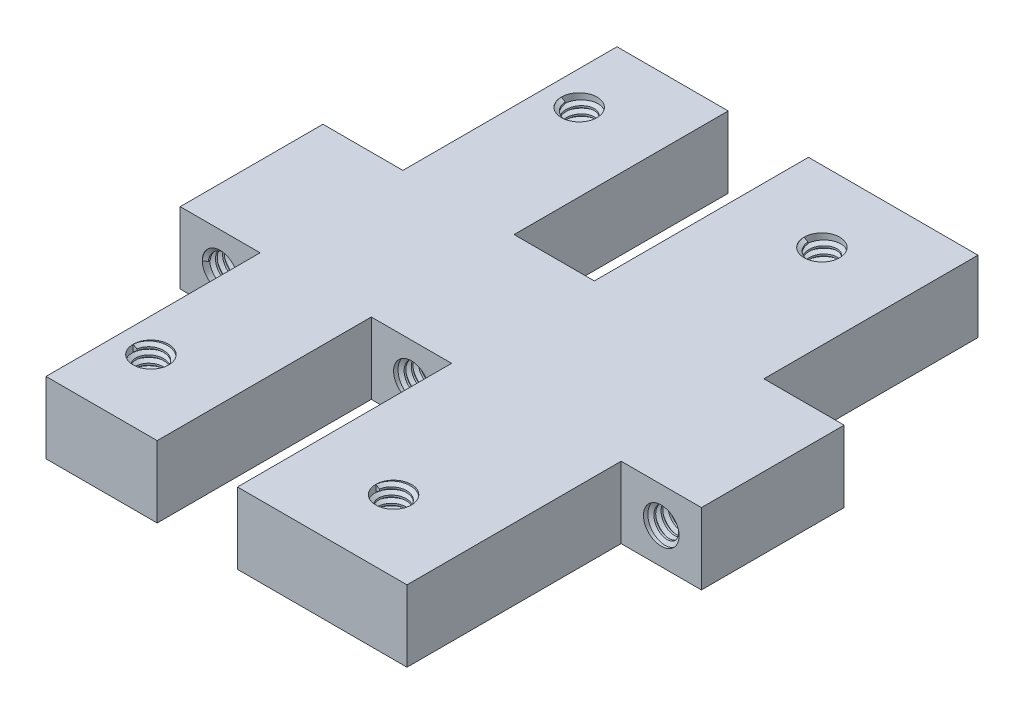
SolidWorks part; units mm, degrees
material "Plain Carbon Steel"
ref_plane "Front Plane" through (0, 0, 0) normal (0, 0, 1) x (1, 0, 0)
ref_plane "Top Plane" through (0, 0, 0) normal (0, 1, 0) x (1, 0, 0)
ref_plane "Right Plane" through (0, 0, 0) normal (1, 0, 0) x (0, 0, -1)
sketch "Sketch1" plane through (0, 0, 0) normal (0, 1, 0) x (1, 0, 0)
  line L0 (0, 51.3938) -> (0, -59.5745) construction
  line L1 (-34.925, 25.4) -> (34.925, 25.4)
  line L2 (-34.925, 25.4) -> (-34.925, -25.4)
  line L3 (-34.925, -25.4) -> (34.925, -25.4)
  line L4 (34.925, 25.4) -> (34.925, -25.4)
  line L5 (-83.1273, 0) -> (79.8286, 0) construction
  dimension "D1" = 50.8
  dimension "D2" = 69.85
extrude "Boss-Extrude1" add sketch "Sketch1" along normal blind 12.7
ref_plane "Plane1" through (22.225, 0, 0) normal (1, 0, 0) x (0, 0, -1)
ref_plane "Plane2" through (-22.225, 0, 0) normal (1, 0, 0) x (0, 0, -1)
sketch "Sketch3" plane through (0, 12.7, 0) normal (0, 1, 0) x (1, 0, 0)
  line L0 (-34.925, -25.4) -> (34.925, -25.4) construction
  line L1 (15.0813, -25.4) -> (29.3688, -25.4)
  line L2 (15.0813, -25.4) -> (15.0813, -12.7)
  line L3 (15.0813, -12.7) -> (29.3688, -12.7)
  line L4 (29.3688, -25.4) -> (29.3688, -12.7)
  line L5 (34.925, 25.4) -> (-34.925, 25.4) construction
  line L6 (-29.3687, -25.4) -> (-15.0812, -25.4)
  line L7 (-29.3687, -25.4) -> (-29.3687, -12.7)
  line L8 (-29.3687, -12.7) -> (-15.0813, -12.7)
  line L9 (-15.0812, -25.4) -> (-15.0813, -12.7)
  line L10 (-29.3687, 25.4) -> (-15.0813, 25.4)
  line L11 (-29.3687, 25.4) -> (-29.3687, 12.7)
  line L12 (-29.3687, 12.7) -> (-15.0812, 12.7)
  line L13 (-15.0813, 25.4) -> (-15.0812, 12.7)
  line L14 (-22.225, 31.6602) -> (-22.225, -34.0161) construction
  line L15 (15.0813, 25.4) -> (29.3687, 25.4)
  line L16 (15.0813, 25.4) -> (15.0812, 12.7)
  line L17 (15.0812, 12.7) -> (29.3687, 12.7)
  line L18 (29.3687, 25.4) -> (29.3687, 12.7)
  line L19 (-22.225, -6.985) -> (-22.225, 6.985) construction
  line L20 (22.225, 30.314) -> (22.225, -34.0161) construction
  line L21 (22.225, -6.985) -> (22.225, 6.985) construction
  dimension "D1" = 12.7
  dimension "D2" = 14.2875
  dimension "D3" = 14.2875
  dimension "D4" = 12.7
  dimension "D5" = 12.7
  dimension "D6" = 14.2875
  dimension "D7" = 14.2875
  dimension "D8" = 12.7
extrude "Cut-Extrude1" cut sketch "Sketch3" against normal blind 12.7
sketch "Sketch4" plane through (0, 0, -12.7) normal (0, 0, -1) x (-1, 0, 0)
  line L0 (-22.225, 6.985) -> (-22.225, -6.985) construction
  line L1 (-34.925, 6.35) -> (43.2714, 6.35) construction
  line L2 (-34.925, 12.7) -> (-34.925, 0) construction
  line L3 (0, 6.985) -> (0, -6.985) construction
  circle A0 centre (-22.225, 6.35) radius 3.175
  circle A1 centre (22.225, 6.35) radius 3.175
  dimension "D1" = 6.35
extrude "Cut-Extrude2" cut sketch "Sketch4" against normal through all
sketch "Sketch6" plane through (0, 12.7, 0) normal (0, 1, 0) x (1, 0, 0)
  line L0 (-34.925, -25.4) -> (-29.3687, -25.4) construction
  line L1 (-34.925, 25.4) -> (-49.149, 25.4)
  line L2 (-34.925, 25.4) -> (-34.925, -25.4)
  line L3 (-34.925, -25.4) -> (-49.149, -25.4)
  line L4 (-49.149, 25.4) -> (-49.149, -25.4)
  dimension "D1" = 14.224
extrude "Boss-Extrude2" add sketch "Sketch6" against normal blind 12.7
sketch "Sketch9" plane through (0, 12.7, 0) normal (0, 1, 0) x (1, 0, 0)
  line L0 (-29.3687, 25.4) -> (-29.3687, 12.7) construction
  line L1 (-49.149, 25.4) -> (-29.3688, 25.4)
  line L2 (-49.149, 25.4) -> (-49.149, 50.8)
  line L3 (-49.149, 50.8) -> (-29.3687, 50.8)
  line L4 (-29.3688, 25.4) -> (-29.3687, 50.8)
  line L5 (-15.0813, 25.4) -> (15.0813, 25.4)
  line L6 (-15.0813, 25.4) -> (-15.0813, 50.8)
  line L7 (-15.0813, 50.8) -> (15.0813, 50.8)
  line L8 (15.0813, 25.4) -> (15.0813, 50.8)
  line L9 (15.0813, 25.4) -> (15.0812, 12.7) construction
  line L10 (-49.149, 25.4) -> (-49.149, -25.4) construction
  line L11 (-29.3687, -25.4) -> (-49.149, -25.4)
  line L12 (-29.3687, -25.4) -> (-29.3687, -50.8)
  line L13 (-29.3687, -50.8) -> (-49.149, -50.8)
  line L14 (-49.149, -25.4) -> (-49.149, -50.8)
  line L15 (15.0813, -25.4) -> (-15.0813, -25.4)
  line L16 (15.0813, -25.4) -> (15.0813, -50.8)
  line L17 (15.0813, -50.8) -> (-15.0812, -50.8)
  line L18 (-15.0813, -25.4) -> (-15.0812, -50.8)
  line L19 (-15.0812, -25.4) -> (-15.0813, -12.7) construction
  dimension "D1" = 25.4
  dimension "D2" = 25.4
  dimension "D3" = 25.4
  dimension "D4" = 25.4
extrude "Boss-Extrude3" add sketch "Sketch9" against normal blind 12.7
sketch "Sketch7" plane through (0, 12.7, 0) normal (0, 1, 0) x (1, 0, 0)
  line L0 (-29.3687, -38.1) -> (40.9011, -38.1) construction
  line L2 (-42.799, -25.4) -> (-42.799, 7.4831) construction
  line L3 (-15.0812, -50.8) -> (15.0813, -50.8) construction
  line L5 (-6.985, 0) -> (6.985, 0) construction
  line L6 (-49.149, 50.8) -> (-49.149, -50.8) construction
  line L7 (34.925, -25.4) -> (34.925, 25.4) construction
  circle A0 centre (-43.18, -38.1) radius 3.175
  circle A1 centre (0, -38.1) radius 3.175
  circle A2 centre (-43.18, 38.1) radius 3.175
  circle A3 centre (0, 38.1) radius 3.175
  dimension "D1" = 6.35
  dimension "D2" = 6.35
  dimension "D3" = 6.35
  dimension "D4" = 34.925
  dimension "D5" = 78.105
  dimension "D6" = 12.7
extrude "Cut-Extrude3" cut sketch "Sketch7" against normal blind 12.7
thread "Thread1" pitch 1.27 method extrude profile "Thread Profile1" start angle 0, offset 0, length 0, pitch 1.27, diameter 6.35
ref_plane "Plane3" through (-46.355, 12.7, 38.1) normal (0, 0, 1) x (-1, 0, 0)
sketch "Thread Profile1" plane through (-46.355, 12.7, 38.1) normal (0, 0, 1) x (-1, 0, 0)
  line L0 (0, 0) -> (0, 1.27) construction
  line L11 (0, 0) -> (0, 1.1112)
  line L12 (0, 1.1112) -> (-0.6874, 0.7144)
  line L13 (-0.6874, 0.7144) -> (-0.6874, 0.3969)
  line L15 (-0.6874, 0.3969) -> (0, 0)
  line L17 (-0.6874, 0.5556) -> (0, 0.5556) construction
  point P2 (0, 0)
  dimension "Pitch" = 1.27
  dimension "Profile_Angle" = 60
  dimension "Profile_Land" = 0.3175
  dimension "Profile_Height" = 0.6874
thread "Thread2" pitch 1.27 method extrude profile "Thread Profile2" start angle 0, offset 0, length 0, pitch 1.27, diameter 6.35
ref_plane "Plane4" through (-3.175, 12.7, 38.1) normal (0, 0, 1) x (-1, 0, 0)
sketch "Thread Profile2" plane through (-3.175, 12.7, 38.1) normal (0, 0, 1) x (-1, 0, 0)
  line L0 (0, 0) -> (0, 1.27) construction
  line L11 (0, 0) -> (0, 1.1112)
  line L12 (0, 1.1112) -> (-0.6874, 0.7144)
  line L13 (-0.6874, 0.7144) -> (-0.6874, 0.3969)
  line L15 (-0.6874, 0.3969) -> (0, 0)
  line L17 (-0.6874, 0.5556) -> (0, 0.5556) construction
  point P2 (0, 0)
  dimension "Pitch" = 1.27
  dimension "Profile_Angle" = 60
  dimension "Profile_Land" = 0.3175
  dimension "Profile_Height" = 0.6874
mirror "Mirror1" about plane through (0, 0, 0) normal (0, 0, 1) of "Thread2", "Thread1"
thread "Thread3" pitch 1.27 method extrude profile "Thread Profile3" start angle 0, offset 0, length 0, pitch 1.27, diameter 6.35
ref_plane "Plane5" through (-19.05, 6.35, -12.7) normal (0, -1, 0) x (1, 0, 0)
sketch "Thread Profile3" plane through (-19.05, 6.35, -12.7) normal (0, -1, 0) x (1, 0, 0)
  line L0 (0, 0) -> (0, 1.27) construction
  line L11 (0, 0) -> (0, 1.1112)
  line L12 (0, 1.1112) -> (-0.6874, 0.7144)
  line L13 (-0.6874, 0.7144) -> (-0.6874, 0.3969)
  line L15 (-0.6874, 0.3969) -> (0, 0)
  line L17 (-0.6874, 0.5556) -> (0, 0.5556) construction
  point P2 (0, 0)
  dimension "Pitch" = 1.27
  dimension "Profile_Angle" = 60
  dimension "Profile_Land" = 0.3175
  dimension "Profile_Height" = 0.6874
thread "Thread4" pitch 1.27 method extrude profile "Thread Profile4" start angle 0, offset 0, length 0, pitch 1.27, diameter 6.35
ref_plane "Plane6" through (25.4, 6.35, -12.7) normal (0, -1, 0) x (1, 0, 0)
sketch "Thread Profile4" plane through (25.4, 6.35, -12.7) normal (0, -1, 0) x (1, 0, 0)
  line L0 (0, 0) -> (0, 1.27) construction
  line L11 (0, 0) -> (0, 1.1112)
  line L12 (0, 1.1112) -> (-0.6874, 0.7144)
  line L13 (-0.6874, 0.7144) -> (-0.6874, 0.3969)
  line L15 (-0.6874, 0.3969) -> (0, 0)
  line L17 (-0.6874, 0.5556) -> (0, 0.5556) construction
  point P2 (0, 0)
  dimension "Pitch" = 1.27
  dimension "Profile_Angle" = 60
  dimension "Profile_Land" = 0.3175
  dimension "Profile_Height" = 0.6874
sketch "Sketch10" plane through (0, 12.7, 0) normal (0, 1, 0) x (1, 0, 0)
  line L1 (29.3687, 25.4) -> (34.925, 25.4)
  line L2 (29.3687, 25.4) -> (29.3687, -25.4)
  line L3 (29.3687, -25.4) -> (34.925, -25.4)
  line L4 (34.925, 25.4) -> (34.925, -25.4)
extrude "Cut-Extrude4" cut sketch "Sketch10" against normal blind 12.7
sketch "Sketch11" plane through (0, 12.7, 0) normal (0, 1, 0) x (1, 0, 0)
  line L0 (-49.149, 50.8) -> (-49.149, -50.8) construction
  line L1 (-49.149, 12.7) -> (-63.373, 12.7)
  line L2 (-49.149, 12.7) -> (-49.149, -12.7)
  line L3 (-49.149, -12.7) -> (-63.373, -12.7)
  line L4 (-63.373, 12.7) -> (-63.373, -12.7)
  line L5 (-29.3687, 12.7) -> (-15.0812, 12.7) construction
  line L6 (-15.0813, -12.7) -> (-29.3687, -12.7) construction
  dimension "D1" = 14.224
extrude "Boss-Extrude4" add sketch "Sketch11" against normal blind 12.7
sketch "Sketch12" plane through (0, 0, 12.7) normal (0, 0, 1) x (1, 0, 0)
  line L0 (-56.261, 12.7) -> (-56.261, 0) construction
  line L1 (-63.373, 12.7) -> (-49.149, 12.7) construction
  line L2 (-63.373, 0) -> (-49.149, 0) construction
  line L3 (-63.373, 6.35) -> (-49.149, 6.35) construction
  line L4 (-63.373, 0) -> (-63.373, 12.7) construction
  line L5 (-49.149, 0) -> (-49.149, 12.7) construction
  circle A0 centre (-56.261, 6.35) radius 3.175
  dimension "D1" = 6.35
extrude "Cut-Extrude5" cut sketch "Sketch12" against normal through all
thread "Thread6" pitch 1.27 method extrude profile "Thread Profile6" start angle 0, offset 0, length 0, pitch 1.27, diameter 6.35
ref_plane "Plane8" through (-59.436, 6.35, 12.7) normal (0, -1, 0) x (-1, 0, 0)
sketch "Thread Profile6" plane through (-59.436, 6.35, 12.7) normal (0, -1, 0) x (-1, 0, 0)
  line L0 (0, 0) -> (0, 1.27) construction
  line L11 (0, 0) -> (0, 1.1112)
  line L12 (0, 1.1112) -> (-0.6874, 0.7144)
  line L13 (-0.6874, 0.7144) -> (-0.6874, 0.3969)
  line L15 (-0.6874, 0.3969) -> (0, 0)
  line L17 (-0.6874, 0.5556) -> (0, 0.5556) construction
  point P2 (0, 0)
  dimension "Pitch" = 1.27
  dimension "Profile_Angle" = 60
  dimension "Profile_Land" = 0.3175
  dimension "Profile_Height" = 0.6874
ref_axis "Axis1" through (-43.18, 0, 38.1) along (0, 1, 0)
ref_axis "Axis2" through (0, 0, -38.1) along (0, 1, 0)
